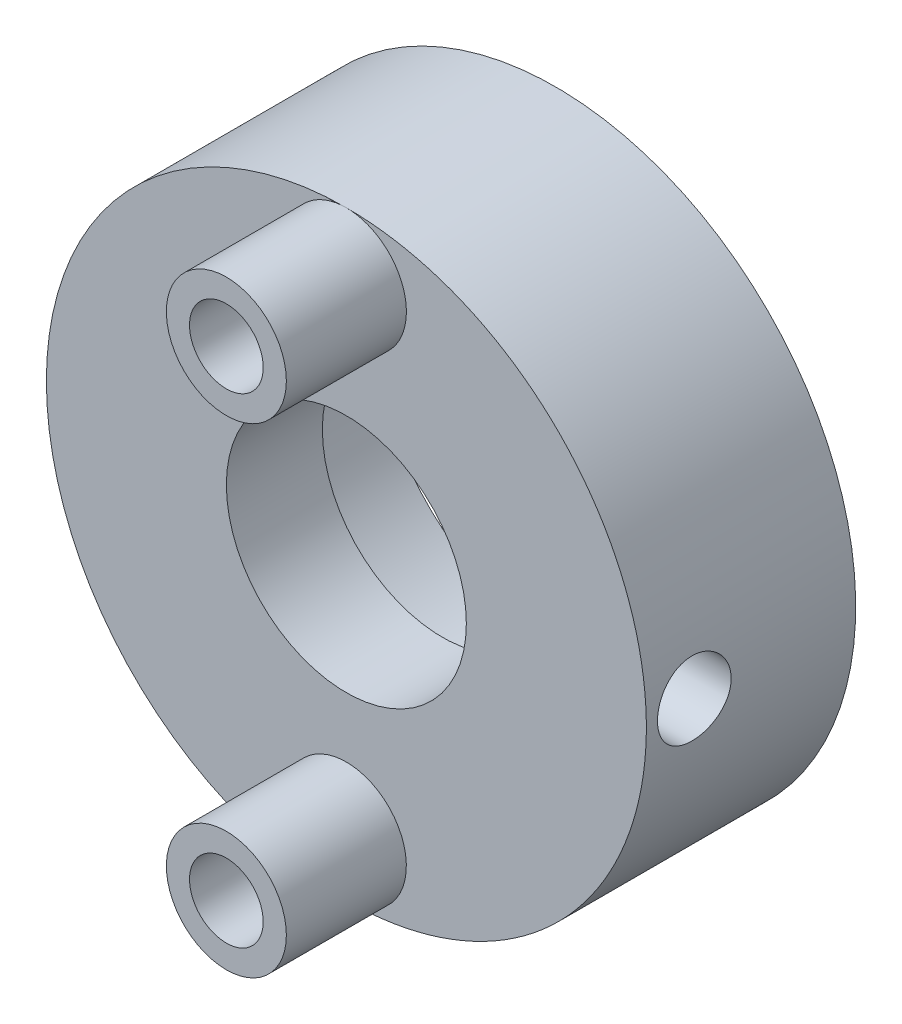
SolidWorks part; units mm, degrees
material "PLA"
ref_plane "Front Plane" through (0, 0, 0) normal (0, 0, 1) x (1, 0, 0)
ref_plane "Top Plane" through (0, 0, 0) normal (0, 1, 0) x (1, 0, 0)
ref_plane "Right Plane" through (0, 0, 0) normal (1, 0, 0) x (0, 0, -1)
sketch "Sketch1" plane through (0, 0, 0) normal (0, 0, 1) x (1, 0, 0)
  line L0 (0, 0) -> (9.3823, 0) construction
  circle A0 centre (0, 0) radius 15.875
  circle A1 centre (0, 12.7) radius 1.95
  circle A2 centre (0, -12.7) radius 1.95
  circle A3 centre (0, 12.7) radius 3.175
  circle A4 centre (0, -12.7) radius 3.175
  circle A5 centre (0, 0) radius 6.35
  dimension "D1" = 31.75
  dimension "D2" = 3.9
  dimension "D4" = 12.7
  dimension "D3" = 12.7
extrude "Boss-Extrude1" add sketch "Sketch1" against normal blind 5.08 contours A0 A4 A3 A5 | A3 A1 | A4 A2 region at (2.1816, 14.8816, 0) region at (-2.1816, -10.5184, 0) region at (10.9078, -10.9078, 0)
extrude "Boss-Extrude2" add sketch "Sketch1<3>" along normal blind 6.35 contours A3 A1 | A4 A2 region at (2.1816, 14.8816, 0) region at (-2.1816, -10.5184, 0)
sketch "Sketch1<3>" plane through (0, 0, 0) normal (0, 0, 1) x (1, 0, 0) same geometry as "Sketch1"
sketch "Sketch2" plane through (0, 0, -5.08) normal (0, 0, -1) x (-1, 0, 0)
  circle A0 centre (0, 0) radius 9.5
  circle A1 centre (0, 0) radius 15.875
  circle A2 centre (0, 0) radius 15.875
  dimension "D2" = 19
  dimension "D1" = 0
extrude "Boss-Extrude3" add sketch "Sketch2" along normal blind 6
ref_plane "Plane1" through (25.4, 0, 0) normal (1, 0, 0) x (0, 0, -1)
sketch "Sketch3" plane through (25.4, 0, 0) normal (1, 0, 0) x (0, 0, -1)
  line L0 (0, 15.875) -> (0, -15.875) construction
  line L1 (0, 15.875) -> (0, -15.875)
  line L2 (11.08, -15.875) -> (11.08, 15.875) construction
  line L3 (11.08, -15.875) -> (11.08, 15.875)
  line L4 (0, 0) -> (5.08, 0) construction
  line L5 (5.08, -6.35) -> (5.08, 6.35) construction
  line L6 (5.08, -6.35) -> (5.08, 6.35)
  circle A0 centre (2.54, 0) radius 1.95
  point P11 (2.54, 0)
  point P12 (2.54, 0)
  dimension "D1" = 3.9
extrude "Cut-Extrude1" cut sketch "Sketch3" against normal up to surface (19.05 mm away) contours L4 A0 | A0 L4 region at (25.4, 0.8276, -2.54) region at (25.4, -0.8276, -2.54) up to face at (6.35, 0, -5.08)
